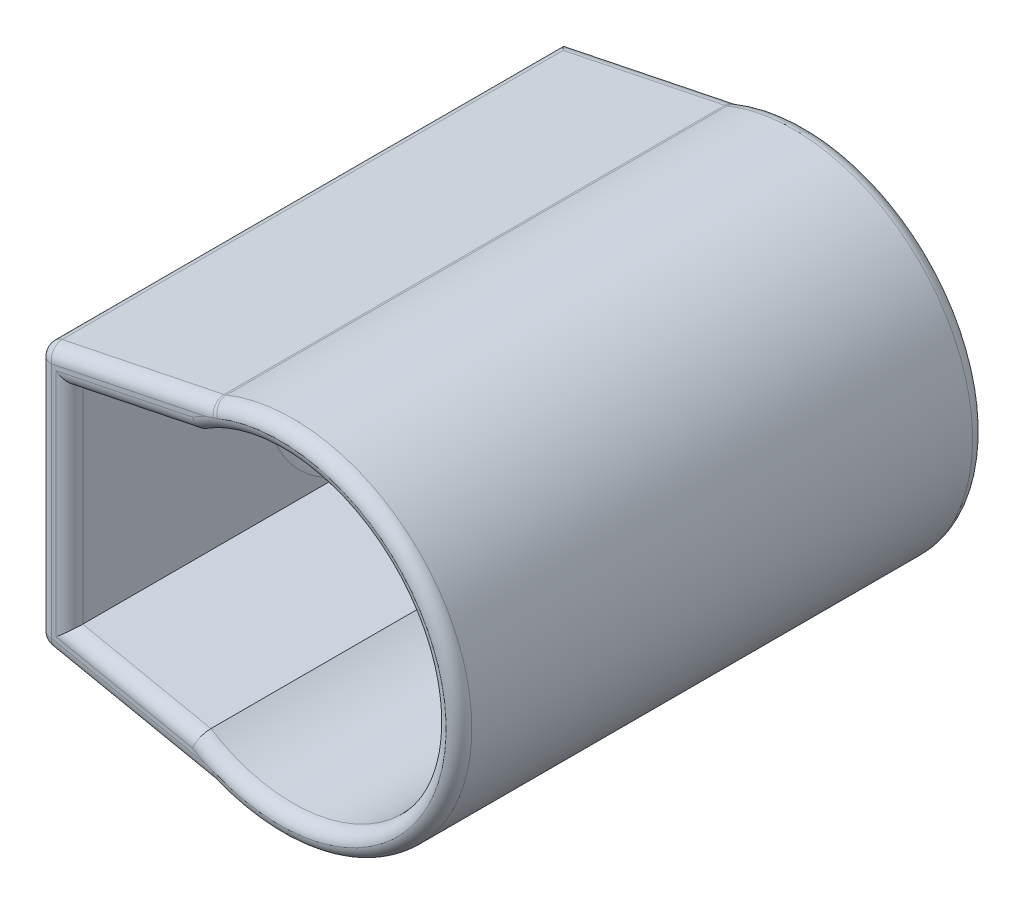
SolidWorks part; units mm, degrees
ref_plane "Front Plane" through (0, 0, 0) normal (0, 0, 1) x (1, 0, 0)
ref_plane "Top Plane" through (0, 0, 0) normal (0, 1, 0) x (1, 0, 0)
ref_plane "Right Plane" through (0, 0, 0) normal (1, 0, 0) x (0, 0, -1)
ref_axis "Axis1" through (-33.0333, 0, 0) along (1, 0, 0)
ref_axis "Axis2" through (0, 24.5224, 0) along (0, -1, 0)
ref_axis "Axis3" through (0, 0, -30.7663) along (0, 0, 1)
sketch "Sketch1" plane through (0, 0, 0) normal (0, 0, 1) x (1, 0, 0)
  line L0 (-9.6437, 14) -> (-9.6437, -14) construction
  line L1 (-33.0333, 0) -> (35.904, 0) construction
  line L2 (-23, 11.25) -> (-23, -11.25) construction
  line L3 (17, 15.24) -> (17, -15.24) construction
  line L4 (-23, 11.25) -> (-9.6437, 14) construction
  line L5 (-9.6437, -14) -> (-23, -11.25) construction
  line L6 (-7.5757, -18.5097) -> (-27, -14.5103)
  line L7 (-27, 14.5103) -> (-27, -14.5103)
  line L8 (-27, 14.5103) -> (-7.5757, 18.5097)
  line L9 (-27, 14.5103) -> (-10.4503, 17.9178) construction
  line L10 (-10.4503, -17.9178) -> (-27, -14.5103) construction
  arc A1 (-7.5757, -18.5097) -> (-7.5757, 18.5097) centre (0, 0) ccw
  circle A2 centre (0, 0) radius 17 construction
  point P2 (-9.6437, 0)
  point P8 (-23, 0)
  point P13 (17, 0)
  dimension "D1" = 40
  dimension "D3" = 34
  dimension "D2" = 28
  dimension "D4" = 22.5
  dimension "D5" = 40
  dimension "D6" = 4
extrude "Boss-Extrude1" add sketch "Sketch1" along normal blind 4
sketch "Sketch2" plane through (0, 0, 4) normal (0, 0, 1) x (1, 0, 0)
  circle A0 centre (0, 0) radius 12
  dimension "D1" = 24
extrude "Boss-Extrude2" add sketch "Sketch2" along normal blind 2.5
sketch "Sketch3" plane through (0, 0, 4) normal (0, 0, 1) x (1, 0, 0)
  line L0 (-27, 14.5103) -> (-27, -14.5103)
  line L1 (-27, -14.5103) -> (-7.5757, -18.5097)
  line L3 (-27, 14.5103) -> (-7.5757, 18.5097)
  line L6 (-23.5, -11.6575) -> (-6.8699, -15.0816)
  line L7 (-23.5, 11.6575) -> (-23.5, -11.6575)
  line L8 (-6.8699, 15.0816) -> (-23.5, 11.6575)
  line L9 (-23.5, -11.6575) -> (-9.1765, -14.6067)
  line L10 (-23.5, 11.6575) -> (-23.5, -11.6575)
  line L11 (-9.1765, 14.6067) -> (-23.5, 11.6575)
  arc A0 (-9.1765, -14.6067) -> (-9.1765, 14.6067) centre (0, 0) ccw
  arc A1 (-7.5757, -18.5097) -> (-7.5757, 18.5097) centre (0, 0) ccw
  arc A2 (-7.5757, -18.5097) -> (-7.5757, 18.5097) centre (0, 0) ccw construction
  dimension "D1" = 34.5
  dimension "D2" = 3.5
extrude "Boss-Extrude3" add sketch "Sketch3" along normal blind 55
sketch "Sketch5" plane through (0, 0, 4) normal (0, 0, 1) x (1, 0, 0)
  line L0 (-9.1765, 14.6067) -> (-23.5, 11.6575)
  line L1 (-23.5, 11.6575) -> (-23.5, -11.6575)
  line L2 (-23.5, -11.6575) -> (-9.1765, -14.6067)
  arc A0 (-9.1765, 14.6067) -> (-9.1765, -14.6067) centre (0, 0) ccw
extrude "Boss-Extrude4" add sketch "Sketch5" along normal blind 9
sketch "Sketch6" plane through (-27, 0, 0) normal (-1, 0, 0) x (0, 0, 1)
  line L0 (-30.7663, 0) -> (71.0523, 0) construction
  line L1 (0, 0) -> (35.45, 0) construction
  line L2 (0, 14.5103) -> (0, -14.5103) construction
  circle A0 centre (24.45, 0) radius 11
  dimension "D1" = 22
  dimension "D2" = 35.45
extrude "Cut-Extrude1" cut sketch "Sketch6" against normal blind 4
fillet "Fillet1" radius 1.5 17 edges at (-17.2879, -16.51, 59) (-17.2879, -16.51, 0) (-17.2879, 16.51, 59) (-17.2879, 16.51, 0) (-7.5757, -18.5097, 29.5) (20, 0, 59) (-7.5757, 18.5097, 29.5) (20, 0, 0) (-27, 14.5103, 29.5) (-27, -14.5103, 29.5) (-16.3382, -13.1321, 59) (-23.5, 0, 59) (-16.3382, 13.1321, 59) (17.25, 0, 59) (-23.5, 0, 13.45) (-27, 0, 35.45) (-27, 0, 59)
